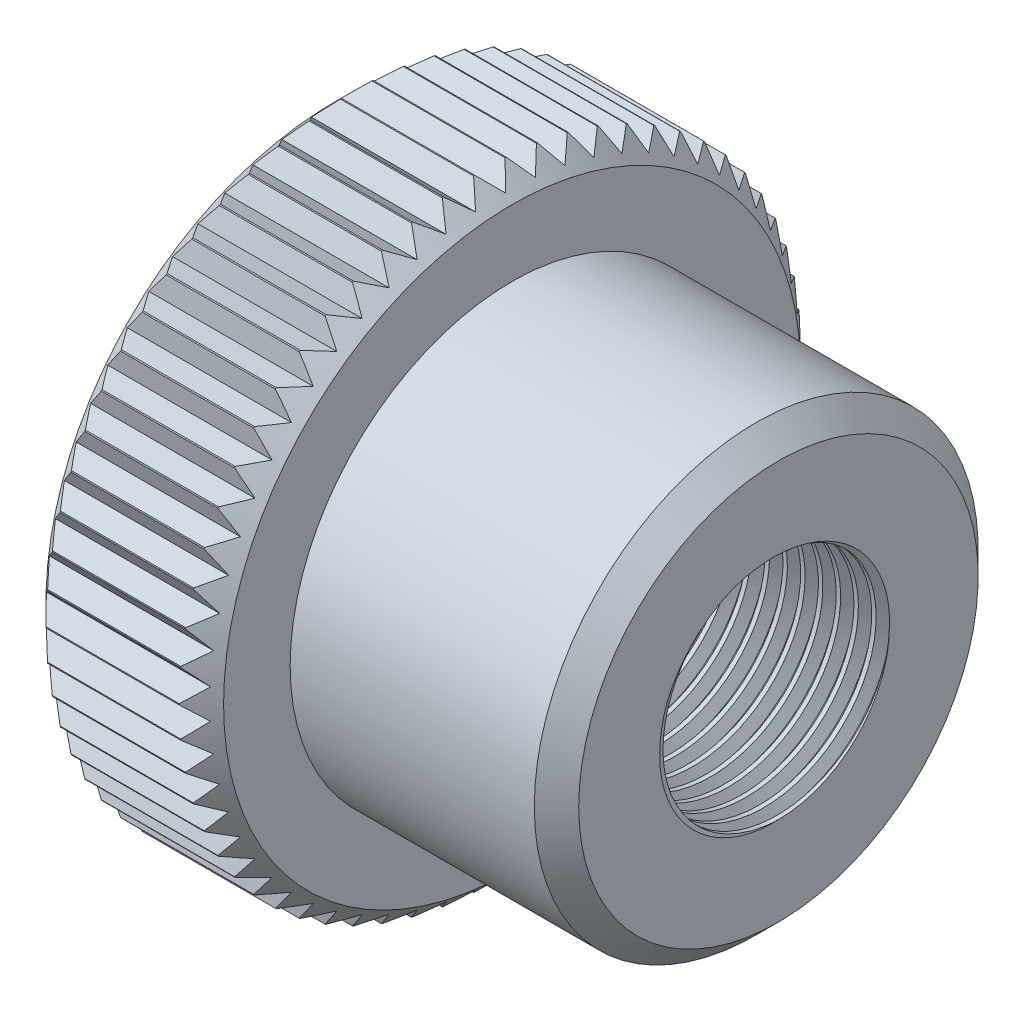
SolidWorks part; units mm, degrees
ref_plane "前视基准面" through (0, 0, 0) normal (0, 0, 1) x (1, 0, 0)
ref_plane "上视基准面" through (0, 0, 0) normal (0, 1, 0) x (1, 0, 0)
ref_plane "右视基准面" through (0, 0, 0) normal (1, 0, 0) x (0, 0, -1)
sketch "Sketch1" plane through (0, 0, 0) normal (0, 0, 1) x (1, 0, 0)
  line L0 (0, 0) -> (10, 0) construction
  line L1 (10, 0) -> (10, 2.5) construction
  line L2 (10, 2.5) -> (0, 2.5)
  line L3 (0, 2.5) -> (0, 7)
  line L4 (0, 7) -> (4, 7)
  line L5 (4, 7) -> (4, 5)
  line L6 (4, 5) -> (10, 5)
  line L7 (10, 5) -> (10, 2.5)
  dimension "D1" = 10
  dimension "D2" = 2.5
  dimension "D3" = 4.5
  dimension "D4" = 2
  dimension "D5" = 4
revolve "Revolve1" add sketch "Sketch1" angle 360 about L0
chamfer "Chamfer1" distance 0.5 angle 45 4 edges at (0, 0, 2.5) (10, 0, 5) (4, 0, 7) (0, 0, 7)
thread "Thread1" pitch 0.4 method cut profile "Sketch3" start angle 0, offset 1, length 0, pitch 0.4, diameter 5
ref_plane "Plane1" through (11, 0, 2.5) normal (0, -1, 0) x (0, 0, 1)
sketch "Sketch3" plane through (11, 0, 2.5) normal (0, -1, 0) x (0, 0, 1)
  line L0 (0, 0) -> (0, 0.4) construction
  line L1 (0, 0) -> (0.2165, 0.125)
  line L2 (0.2165, 0.125) -> (0.2165, 0.175)
  line L3 (0.2165, 0.175) -> (0, 0.3)
  line L4 (0.2165, 0.15) -> (0, 0.15) construction
  line L11 (0, 0) -> (0, 0.3)
  point P2 (0, 0)
  dimension "Pitch" = 0.4
  dimension "Profile_Angle" = 60
  dimension "Profile_Land" = 0.05
  dimension "Profile_Height" = 0.2165
sketch "Sketch6" plane through (0, 0, 0) normal (-1, 0, 0) x (0, 0, 1)
  line L0 (-2, 8.65) -> (0, 6.65)
  line L1 (0, 6.65) -> (2, 8.65)
  line L2 (2, 8.65) -> (-2, 8.65)
  point P4 (0, 0)
  point P7 (0, 6.5)
  point P8 (0, 6.5)
  dimension "D1" = 2
  dimension "D2" = 6.65
extrude "Cut-Extrude1" cut sketch "Sketch6" against normal blind 10
pattern_circular "CirPattern1" count 62 over 360 about axis through (0, 0, 0) along (-1, 0, 0) of "Cut-Extrude1"
